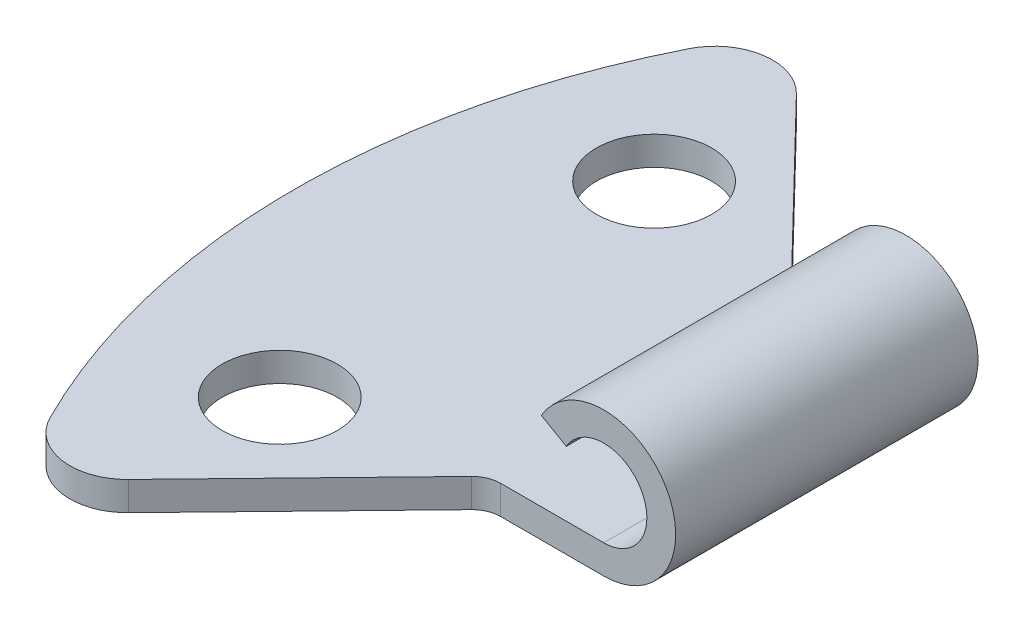
SolidWorks part; units mm, degrees
material "Acciaio inossidabile fuso"
ref_plane "Piano frontale" through (0, 0, 0) normal (0, 0, 1) x (1, 0, 0)
ref_plane "Piano superiore" through (0, 0, 0) normal (0, 1, 0) x (1, 0, 0)
ref_plane "Piano destro" through (0, 0, 0) normal (1, 0, 0) x (0, 0, -1)
sketch "Schizzo1" plane through (0, 0, 0) normal (0, 0, 1) x (1, 0, 0)
  line L0 (8, 1) -> (8, 2.5) construction
  line L1 (-8, 1) -> (8, 1)
  line L2 (-8, 1) -> (-8, 0)
  line L3 (-8, 0) -> (8, 0)
  line L5 (5.8349, 3.75) -> (6.701, 3.25)
  arc A0 (8, 0) -> (5.8349, 3.75) centre (8, 2.5) ccw
  arc A1 (8, 1) -> (6.701, 3.25) centre (8, 2.5) ccw
  point P6 (0, 0)
  dimension "D3" = 3
  dimension "D4" = 1
  dimension "D1" = 16
  dimension "D2" = 1
  dimension "D5" = 120
extrude "Estrusione-Estrusione1" add sketch "Schizzo1" along normal blind 27
sketch "Schizzo2" plane through (0, 1, 0) normal (0, 1, 0) x (1, 0, 0)
  line L0 (-2, -20) -> (-2, -7) construction
  line L1 (-8, -27) -> (-8, 0) construction
  line L2 (-2, -13.5) -> (-8, -13.5) construction
  line L3 (12, -8.25) -> (4.4233, -8.25)
  line L5 (12, -18.75) -> (4.4233, -18.75)
  line L6 (4, -8.25) -> (4, -18.75) construction
  line L7 (4, -13.5) -> (-2, -13.5) construction
  line L8 (3.7054, -19.0539) -> (-2.1521, -25.0944)
  line L9 (8, -27) -> (-8, -27) construction
  line L10 (3.7054, -7.9461) -> (-2.1521, -1.9056)
  line L11 (8, 0) -> (-8, 0) construction
  line L12 (12, -18.75) -> (12, -27)
  line L13 (12, -27) -> (-8, -27)
  line L14 (-8, -27) -> (-8, -13.5)
  line L15 (12, 0) -> (12, -8.25)
  line L16 (12, 0) -> (-8, 0)
  line L17 (-8, 0) -> (-8, -13.5)
  circle A0 centre (-2, -7) radius 2
  circle A1 centre (-2, -20) radius 2
  arc A2 (-5.3762, -24.5977) -> (-5.3762, -2.4023) centre (16.7813, -13.5) cw
  arc A3 (-2.1521, -1.9056) -> (-5.3762, -2.4023) centre (-3.5879, -3.2979) ccw
  arc A4 (-2.1521, -25.0944) -> (-5.3762, -24.5977) centre (-3.5879, -23.7021) cw
  arc A5 (4.4233, -18.75) -> (3.7054, -19.0539) centre (4.4233, -19.75) ccw
  arc A6 (4.4233, -8.25) -> (3.7054, -7.9461) centre (4.4233, -7.25) cw
  point P26 (-4, 0)
  point P29 (-4, -27)
  line M9 (8, 0) -> (-8, 0)
  line M10 (-8, 0) -> (-8, -27)
  line M11 (-8, -27) -> (8, -27)
  line M12 (8, -27) -> (8, 0)
  dimension "D2" = 4
  dimension "D8" = 24.7813
  dimension "D9" = 2
  dimension "D10" = 1
  dimension "D1" = 13
  dimension "D3" = 6
  dimension "D4" = 10.5
  dimension "D5" = 6
  dimension "D6" = 4
  dimension "D7" = 4
  dimension "D11" = 20
extrude "Taglio-Estrusione1" cut sketch "Schizzo2" against normal blind 27 and the other way blind 27 contours L5 A5 L8 A4 A2 M10 M11 M12 | A6 L3 A2 A3 L10 M12 M9 M10 | L13 L12 L5 M12 | L15 L16 L3 M12 | A1 | A0 region at (10, 1, 4.125) region at (1.3746, 1, 3.3636) region at (1.3746, 1, 23.6364) region at (10, 1, 22.875)
